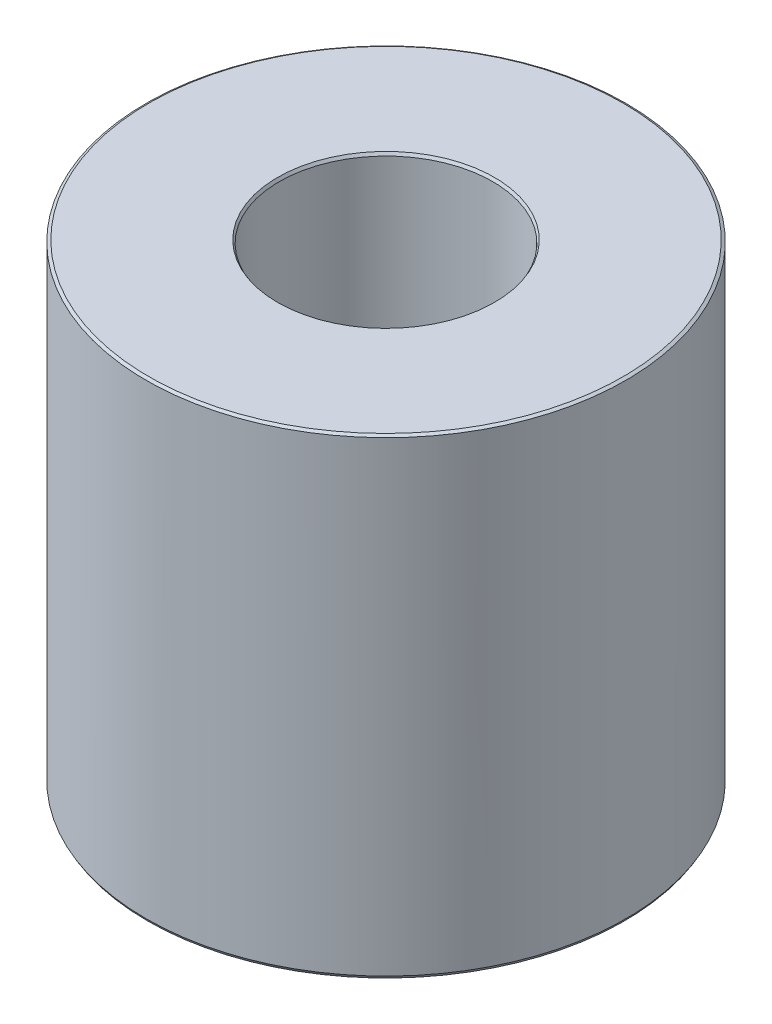
SolidWorks part; units mm, degrees
ref_plane "Front Plane" through (0, 0, 0) normal (0, 0, 1) x (1, 0, 0)
ref_plane "Top Plane" through (0, 0, 0) normal (0, 1, 0) x (1, 0, 0)
ref_plane "Right Plane" through (0, 0, 0) normal (1, 0, 0) x (0, 0, -1)
sketch "Sketch1" plane through (0, 0, 0) normal (0, 1, 0) x (1, 0, 0)
  circle A0 centre (0, 0) radius 40
  dimension "SLEEVE_OD" = 80
extrude "Boss-Extrude1" add sketch "Sketch1" along normal blind 78.5004
sketch "Sketch2" plane through (0, 0, 0) normal (0, 1, 0) x (1, 0, 0)
  circle A0 centre (0, 0) radius 17.7984
  dimension "BORE_D" = 35.5967
extrude "Cut-Extrude1" cut sketch "Sketch2" along normal through all
chamfer "Chamfer1" distance 0.2747 angle 60 4 edges at (0, 78.5004, 17.7984) (0, 0, 17.7984) (0, 0, 40) (0, 78.5004, 40) first distance on face at (0, 78.5004, 17.7984) first distance on face at (0, 0, 17.7984) first distance on face at (0, 78.5004, 40)
